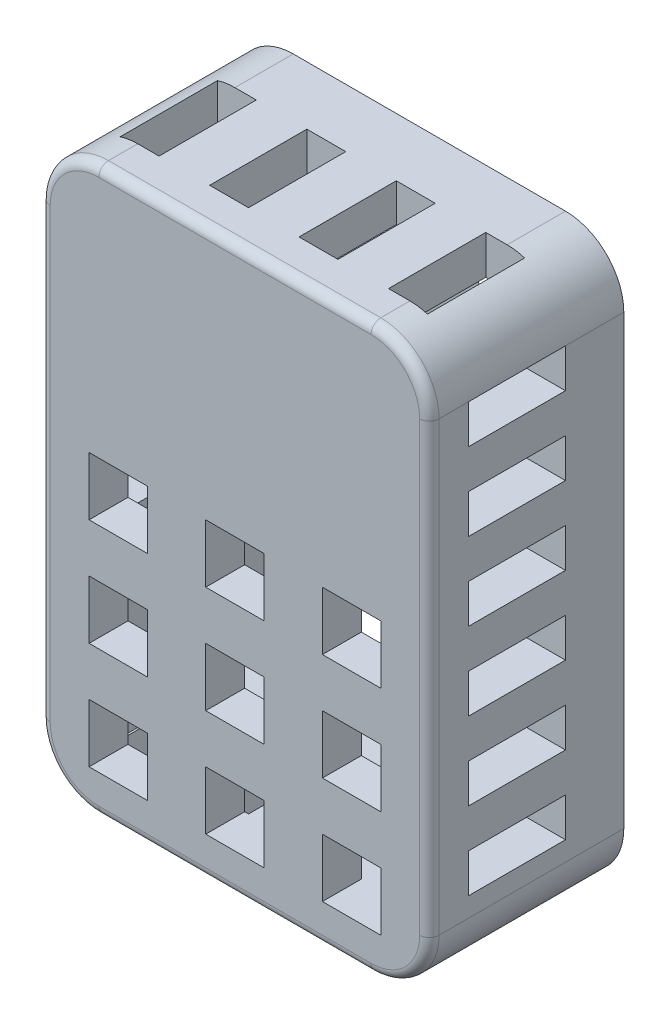
SolidWorks part; units mm, degrees
ref_plane "Front Plane" through (0, 0, 0) normal (0, 0, 1) x (1, 0, 0)
ref_plane "Top Plane" through (0, 0, 0) normal (0, 1, 0) x (1, 0, 0)
ref_plane "Right Plane" through (0, 0, 0) normal (1, 0, 0) x (0, 0, -1)
sketch "Sketch2" plane through (0, 0, 0) normal (0, 0, 1) x (1, 0, 0)
  line L1 (10, -14.5) -> (-10, -14.5)
  line L2 (10, -14.5) -> (10, 14.5)
  line L3 (10, 14.5) -> (-10, 14.5)
  line L4 (-10, -14.5) -> (-10, 14.5)
  line L5 (10, -14.5) -> (-10, 14.5) construction
  line L6 (10, 14.5) -> (-10, -14.5) construction
  point P0 (0, 0)
  dimension "D1" = 20
  dimension "D2" = 29
extrude "Boss-Extrude1" add sketch "Sketch2" along normal blind 10
shell "Shell1" thickness 2 removed face at (0, 0, 0)
sketch "Sketch3" plane through (10, 0, 0) normal (1, 0, 0) x (0, 0, -1)
  line L0 (-10, 14.5) -> (0, 14.5) construction
  line L1 (-8, 11.5) -> (-3, 11.5)
  line L2 (-8, 11.5) -> (-8, 9.5)
  line L3 (-8, 9.5) -> (-3, 9.5)
  line L4 (-3, 11.5) -> (-3, 9.5)
  line L5 (-10, -14.5) -> (-10, 14.5) construction
  line L6 (0, 55) -> (0, -55) construction
  line L7 (-8, 7.5) -> (-3, 7.5)
  line L8 (-8, 7.5) -> (-8, 5.5)
  line L9 (-8, 5.5) -> (-3, 5.5)
  line L10 (-3, 7.5) -> (-3, 5.5)
  line L11 (-8, 3.5) -> (-3, 3.5)
  line L12 (-8, 3.5) -> (-8, 1.5)
  line L13 (-8, 1.5) -> (-3, 1.5)
  line L14 (-3, 3.5) -> (-3, 1.5)
  line L15 (-8, -0.5) -> (-3, -0.5)
  line L16 (-8, -0.5) -> (-8, -2.5)
  line L17 (-8, -2.5) -> (-3, -2.5)
  line L18 (-3, -0.5) -> (-3, -2.5)
  line L19 (-8, -4.5) -> (-3, -4.5)
  line L20 (-8, -4.5) -> (-8, -6.5)
  line L21 (-8, -6.5) -> (-3, -6.5)
  line L22 (-3, -4.5) -> (-3, -6.5)
  line L23 (-8, -8.5) -> (-3, -8.5)
  line L24 (-8, -8.5) -> (-8, -10.5)
  line L25 (-8, -10.5) -> (-3, -10.5)
  line L26 (-3, -8.5) -> (-3, -10.5)
  dimension "D1" = 3
  dimension "D2" = 2
  dimension "D3" = 3
  dimension "D4" = 2
  dimension "D5" = 6
extrude "Cut-Extrude1" cut sketch "Sketch3" against normal up to surface (20 mm away) up to face at (-10, 0, 5)
sketch "Sketch4" plane through (0, 14.5, 0) normal (0, 1, 0) x (1, 0, 0)
  line L0 (10, -10) -> (-10, -10) construction
  line L1 (-7.9, -3) -> (-5.9, -3)
  line L2 (-7.9, -3) -> (-7.9, -8)
  line L3 (-7.9, -8) -> (-5.9, -8)
  line L4 (-5.9, -3) -> (-5.9, -8)
  line L5 (-55, 0) -> (55, 0) construction
  line L6 (-3.3, -3) -> (-1.3, -3)
  line L7 (-3.3, -3) -> (-3.3, -8)
  line L8 (-3.3, -8) -> (-1.3, -8)
  line L9 (-1.3, -3) -> (-1.3, -8)
  line L10 (1.3, -3) -> (3.3, -3)
  line L11 (1.3, -3) -> (1.3, -8)
  line L12 (1.3, -8) -> (3.3, -8)
  line L13 (3.3, -3) -> (3.3, -8)
  line L14 (5.9, -3) -> (7.9, -3)
  line L15 (5.9, -3) -> (5.9, -8)
  line L16 (5.9, -8) -> (7.9, -8)
  line L17 (7.9, -3) -> (7.9, -8)
  line L18 (-10, -10) -> (-10, 0) construction
  dimension "D1" = 2
  dimension "D2" = 3
  dimension "D3" = 2
  dimension "D5" = 2.1
  dimension "D4" = 4
extrude "Cut-Extrude2" cut sketch "Sketch4" against normal up to surface (29 mm away) up to face at (0, -14.5, 5)
fillet "Fillet1" radius 3 4 edges at (10, -14.5, 5) (-10, -14.5, 5) (-10, 14.5, 5) (10, 14.5, 5)
sketch "Sketch7" plane through (0, 0, 10) normal (0, 0, 1) x (1, 0, 0)
  line L0 (7.5, -1.5) -> (4.5, -1.5)
  line L1 (1.5, -1.5) -> (-1.5, -1.5)
  line L2 (1.5, -1.5) -> (1.5, 1.5)
  line L3 (1.5, 1.5) -> (-1.5, 1.5)
  line L4 (-1.5, -1.5) -> (-1.5, 1.5)
  line L5 (1.5, -1.5) -> (-1.5, 1.5) construction
  line L6 (1.5, 1.5) -> (-1.5, -1.5) construction
  line L7 (7.5, -1.5) -> (7.5, 1.5)
  line L8 (7.5, 1.5) -> (4.5, 1.5)
  line L9 (4.5, -1.5) -> (4.5, 1.5)
  line L10 (7.5, -1.5) -> (4.5, 1.5) construction
  line L11 (7.5, 1.5) -> (4.5, -1.5) construction
  line L12 (-4.5, -1.5) -> (-7.5, -1.5)
  line L13 (-4.5, -1.5) -> (-4.5, 1.5)
  line L14 (-4.5, 1.5) -> (-7.5, 1.5)
  line L15 (-7.5, -1.5) -> (-7.5, 1.5)
  line L16 (-4.5, -1.5) -> (-7.5, 1.5) construction
  line L17 (-4.5, 1.5) -> (-7.5, -1.5) construction
  line L54 (7.5, -7) -> (4.5, -7)
  line L55 (1.5, -7) -> (-1.5, -7)
  line L56 (1.5, -7) -> (1.5, -4)
  line L57 (1.5, -4) -> (-1.5, -4)
  line L58 (-1.5, -7) -> (-1.5, -4)
  line L59 (7.5, -7) -> (7.5, -4)
  line L60 (7.5, -4) -> (4.5, -4)
  line L61 (4.5, -7) -> (4.5, -4)
  line L62 (-4.5, -7) -> (-7.5, -7)
  line L63 (-4.5, -7) -> (-4.5, -4)
  line L64 (-4.5, -4) -> (-7.5, -4)
  line L65 (-7.5, -7) -> (-7.5, -4)
  line L66 (1.5, -7) -> (-1.5, -4) construction
  line L67 (1.5, -4) -> (-1.5, -7) construction
  line L68 (7.5, -7) -> (4.5, -4) construction
  line L69 (7.5, -4) -> (4.5, -7) construction
  line L70 (-4.5, -7) -> (-7.5, -4) construction
  line L71 (-4.5, -4) -> (-7.5, -7) construction
  line L72 (7.5, -12.5) -> (4.5, -12.5)
  line L73 (1.5, -12.5) -> (-1.5, -12.5)
  line L74 (1.5, -12.5) -> (1.5, -9.5)
  line L75 (1.5, -9.5) -> (-1.5, -9.5)
  line L76 (-1.5, -12.5) -> (-1.5, -9.5)
  line L77 (7.5, -12.5) -> (7.5, -9.5)
  line L78 (7.5, -9.5) -> (4.5, -9.5)
  line L79 (4.5, -12.5) -> (4.5, -9.5)
  line L80 (-4.5, -12.5) -> (-7.5, -12.5)
  line L81 (-4.5, -12.5) -> (-4.5, -9.5)
  line L82 (-4.5, -9.5) -> (-7.5, -9.5)
  line L83 (-7.5, -12.5) -> (-7.5, -9.5)
  line L84 (1.5, -12.5) -> (-1.5, -9.5) construction
  line L85 (1.5, -9.5) -> (-1.5, -12.5) construction
  line L86 (7.5, -12.5) -> (4.5, -9.5) construction
  line L87 (7.5, -9.5) -> (4.5, -12.5) construction
  line L88 (-4.5, -12.5) -> (-7.5, -9.5) construction
  line L89 (-4.5, -9.5) -> (-7.5, -12.5) construction
  point P0 (0, 0)
  point P6 (6, 0)
  point P12 (-6, 0)
  point P48 (0, -5.5)
  point P53 (6, -5.5)
  point P58 (-6, -5.5)
  point P63 (0, -11)
  point P68 (6, -11)
  point P73 (-6, -11)
  dimension "D3" = 2
  dimension "D4" = 2
  dimension "D6" = 3
extrude "Cut-Extrude3" cut sketch "Sketch7" against normal up to surface (2 mm away)
fillet "Fillet3" radius 0.5 8 edges at (9.1213, 13.6213, 10) (0, 14.5, 10) (-9.1213, 13.6213, 10) (-10, 0, 10) (-9.1213, -13.6213, 10) (0, -14.5, 10) (9.1213, -13.6213, 10) (10, 0, 10)
sketch "Sketch8" plane through (0, 0, 8) normal (0, 0, -1) x (-1, 0, 0)
  circle A0 centre (0, 7.5154) radius 2.8
  circle A1 centre (0, 7.5154) radius 5.2
  dimension "D1" = 2.4
extrude "Boss-Extrude2" add sketch "Sketch8" along normal blind 6.4
